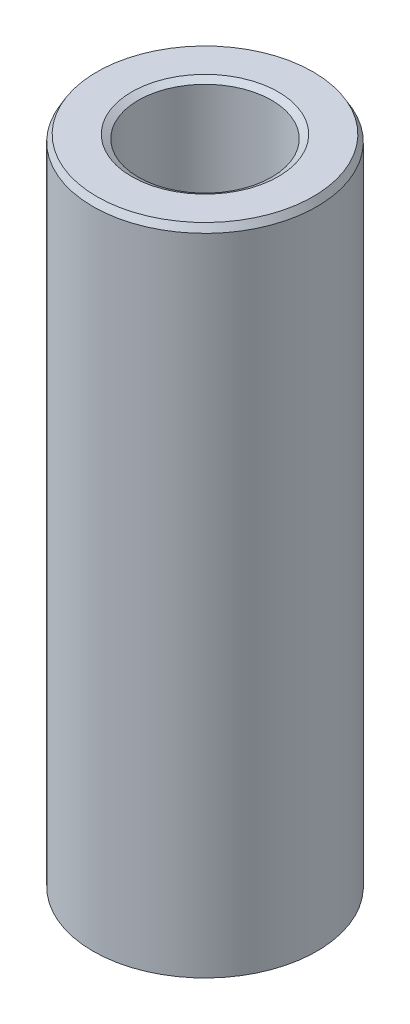
SolidWorks part; units mm, degrees
ref_plane "Front Plane" through (0, 0, 0) normal (0, 0, 1) x (1, 0, 0)
ref_plane "Top Plane" through (0, 0, 0) normal (0, 1, 0) x (1, 0, 0)
ref_plane "Right Plane" through (0, 0, 0) normal (1, 0, 0) x (0, 0, -1)
sketch "Sketch1" plane through (0, 0, 0) normal (0, 1, 0) x (1, 0, 0)
  circle A0 centre (0, 0) radius 40
  dimension "SLEEVE_OD" = 80
extrude "Boss-Extrude1" add sketch "Sketch1" along normal blind 234.1479
sketch "Sketch2" plane through (0, 0, 0) normal (0, 1, 0) x (1, 0, 0)
  circle A0 centre (0, 0) radius 23.8197
  dimension "BORE_D" = 47.6393
extrude "Cut-Extrude1" cut sketch "Sketch2" along normal through all
chamfer "Chamfer1" distance 2.3917 angle 30 4 edges at (0, 234.1479, 23.8197) (0, 0, 23.8197) (0, 0, 40) (0, 234.1479, 40) first distance on face at (0, 234.1479, 23.8197) first distance on face at (0, 0, 23.8197) first distance on face at (0, 234.1479, 40)
